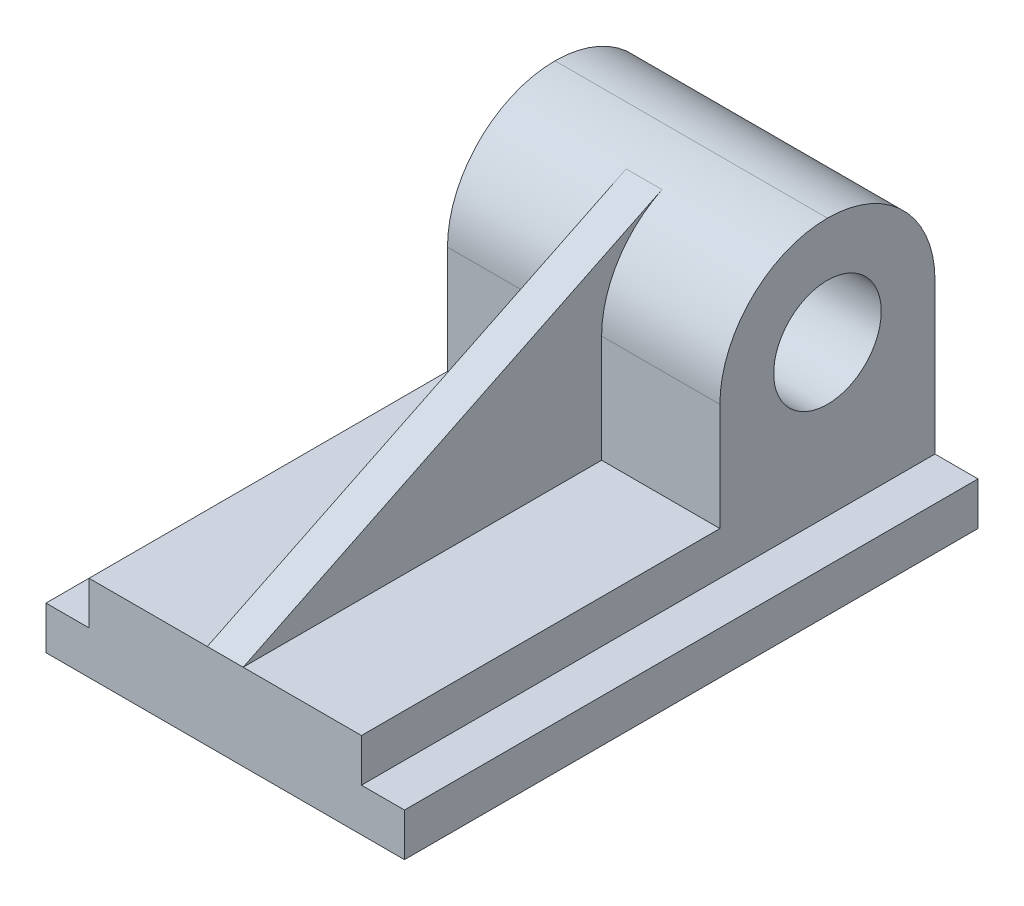
SolidWorks part; units mm, degrees
ref_plane "Front Plane" through (0, 0, 0) normal (0, 0, 1) x (1, 0, 0)
ref_plane "Top Plane" through (0, 0, 0) normal (0, 1, 0) x (1, 0, 0)
ref_plane "Right Plane" through (0, 0, 0) normal (1, 0, 0) x (0, 0, -1)
sketch "Sketch2" plane through (0, 0, 0) normal (1, 0, 0) x (0, 0, -1)
  line L1 (-80, 6) -> (20, 6)
  line L2 (-80, 6) -> (-80, -6)
  line L3 (-80, -6) -> (80, -6)
  line L4 (80, 6) -> (80, -6)
  line L5 (-80, 6) -> (80, -6) construction
  line L6 (-80, -6) -> (0, 0) construction
  line L8 (80, 6) -> (80, 66)
  line L9 (80, 66) -> (20, 66)
  line L10 (20, 6) -> (20, 66)
  point P0 (0, 0)
  dimension "D1" = 160
  dimension "D2" = 12
  dimension "D3" = 60
  dimension "D4" = 60
extrude "Boss-Extrude2" add sketch "Sketch2" along normal blind 38 and the other way blind 38
fillet "Fillet1" radius 30 2 edges at (0, 66, -80) (0, 66, -20)
sketch "Sketch3" plane through (0, 0, 0) normal (1, 0, 0) x (0, 0, -1)
  line L0 (20, 6) -> (50, 6) construction
  line L1 (50, 6) -> (50, 36) construction
  circle A0 centre (50, 36) radius 15
  dimension "D3" = 30
  dimension "D1" = 30
  dimension "D2" = 30
extrude "Cut-Extrude1" cut sketch "Sketch3" against normal through all both and the other way through all
sketch "Sketch5" plane through (0, 0, 0) normal (0, 0, 1) x (1, 0, 0)
  line L0 (0, 0) -> (0, -12) construction
  line L2 (-50, -6) -> (50, -6)
  line L3 (-50, -6) -> (-50, -18)
  line L4 (-50, -18) -> (50, -18)
  line L5 (50, -6) -> (50, -18)
  line L6 (-50, -6) -> (50, -18) construction
  line L7 (-50, -18) -> (50, -6) construction
  dimension "D1" = 12
  dimension "D2" = 12
  dimension "D3" = 100
extrude "Boss-Extrude3" add sketch "Sketch5" along normal up to surface and the other way up to surface up to face at (0, 0, 80) other way up to face at (0, 15, -80)
sketch "Sketch6" plane through (0, 0, 0) normal (0, 0, 1) x (1, 0, 0)
  line L0 (0, 0) -> (0, -17.61) construction
  line L1 (0, -17.61) -> (26, -17.61) construction
  line L2 (0, -17.61) -> (-26, -17.61) construction
  line L4 (-26, -17.61) -> (-26, -7.8594)
  line L5 (-26, -7.8594) -> (26, -7.8594)
  line L6 (26, -7.8594) -> (26, -17.61)
  dimension "D1" = 26
  dimension "D2" = 26
  dimension "D3" = 9.7506
sketch "Sketch7" plane through (0, 0, 0) normal (1, 0, 0) x (0, 0, -1)
  line L0 (-80, 6) -> (36.8539, 62.9663)
  arc A0 (50, 66) -> (20, 36) centre (50, 36) ccw construction
rib "Rib1" sketch "Sketch7" sketch "Sketch7" thickness 10 extrusion direction parallel to sketch draft on no parameters "D1"=10
